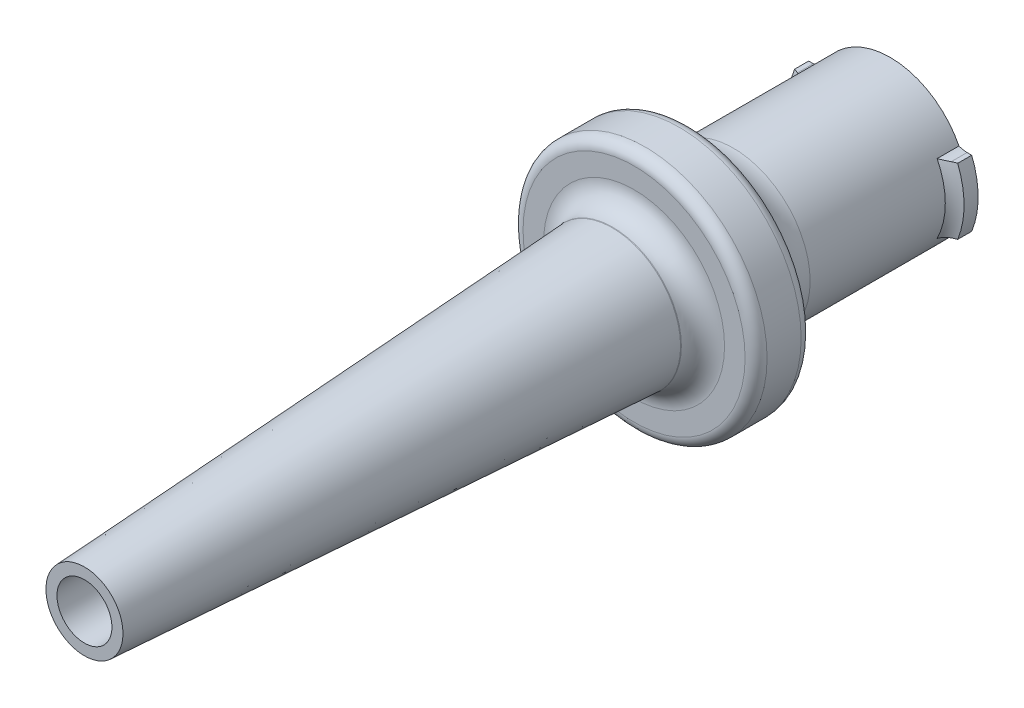
SolidWorks part; units mm, degrees
ref_plane "Front Plane" through (0, 0, 0) normal (0, 0, 1) x (1, 0, 0)
ref_plane "Top Plane" through (0, 0, 0) normal (0, 1, 0) x (1, 0, 0)
ref_plane "Right Plane" through (0, 0, 0) normal (1, 0, 0) x (0, 0, -1)
sketch "Sketch1" plane through (0, 0, 0) normal (0, 0, 1) x (1, 0, 0)
  line L1 (4, 1.5) -> (-4, 1.5)
  line L2 (4, 1.5) -> (4, -1.5)
  line L3 (4, -1.5) -> (-4, -1.5)
  line L4 (-4, 1.5) -> (-4, -1.5)
  circle A0 centre (0, 0) radius 4
  dimension "D1" = 4
  dimension "D2" = 4
  dimension "D3" = 1.5
  dimension "D4" = 3
extrude "Boss-Extrude1" add sketch "Sketch1" along normal blind 0.64 contours L1 A0 L3 region at (0, 0, 0)
sketch "Sketch2" plane through (0, 0, 0) normal (0, 0, -1) x (-1, 0, 0)
  circle A1 centre (0, 0) radius 3.3
extrude "Boss-Extrude2" add sketch "Sketch2" against normal blind 9.1
sketch "Sketch3" plane through (0, 0, 0) normal (0, 0, -1) x (-1, 0, 0)
  circle A0 centre (0, 0) radius 2.13
extrude "Cut-Extrude2" cut sketch "Sketch3" against normal blind 9.1 draft 4
sketch "Sketch4" plane through (0, 0, 9.1) normal (0, 0, 1) x (1, 0, 0)
  circle A0 centre (0, 0) radius 1.4937
  circle A1 centre (0, 0) radius 5.55
extrude "Boss-Extrude3" add sketch "Sketch4" along normal blind 2.55
sketch "Sketch8" plane through (0, 0, 11.65) normal (0, 0, 1) x (1, 0, 0)
  circle A0 centre (0, 0) radius 1.4937
  dimension "D1" = 2.9873
extrude "Boss-Extrude5" add sketch "Sketch8" along normal blind 25 separate body
sketch "Sketch9" plane through (0, 0, 11.65) normal (0, 0, 1) x (1, 0, 0)
  circle A0 centre (0, 0) radius 3.15
extrude "Boss-Extrude6" add sketch "Sketch9" along normal blind 25 draft 2
sketch "Sketch11" plane through (0, 0, 36.65) normal (0, 0, 1) x (1, 0, 0)
  circle A0 centre (0, 0) radius 1.495
extrude "Cut-Extrude7" cut sketch "Sketch11" against normal blind 25
fillet "Fillet6" radius 1 1 edges at (3.3, 0, 0.64)
fillet "Fillet7" radius 1 1 edges at (-3.3, 0, 0.64)
fillet "Fillet8" radius 1 4 edges at (-2.9394, -1.5, 0.797) (2.9394, -1.5, 0.797) (2.9394, 1.5, 0.797) (-2.9394, 1.5, 0.797)
fillet "Fillet10" radius 1 1 edges at (3.15, 0, 11.65)
fillet "Fillet11" radius 0.5 2 edges at (5.55, 0, 11.65) (5.55, 0, 9.1)
sketch "Sketch12" plane through (0, 0, 0) normal (0, 0, -1) x (-1, 0, 0)
  circle A0 centre (0, 0) radius 2.2
extrude "Cut-Extrude8" cut sketch "Sketch12" against normal blind 8 draft 5
sketch "Sketch14" plane through (0, 0, 0) normal (0, 0, -1) x (-1, 0, 0)
  circle A0 centre (0, 0) radius 2.25
extrude "Cut-Extrude9" cut sketch "Sketch14" against normal blind 9.1 draft 3
sketch "Sketch15" plane through (0, 0, 0) normal (0, 0, -1) x (-1, 0, 0)
  circle A0 centre (0, 0) radius 3.3
  circle A1 centre (0, 0) radius 3.5
extrude "Boss-Extrude7" add sketch "Sketch15" against normal blind 9
sketch "Sketch16" plane through (0, 0, 0) normal (0, 0, -1) x (-1, 0, 0)
  circle A0 centre (0, 0) radius 2.5
extrude "Cut-Extrude11" cut sketch "Sketch16" against normal blind 9 draft 2.5
sketch "Sketch19" plane through (0, 0, 36.65) normal (0, 0, 1) x (1, 0, 0)
  circle A0 centre (0, 0) radius 2
  circle A1 centre (0, 0) radius 3.1163
extrude "Cut-Extrude12" cut sketch "Sketch19" against normal blind 24
sketch "Sketch20" plane through (0, 0, 36.65) normal (0, 0, 1) x (1, 0, 0)
  circle A0 centre (0, 0) radius 1.25
  circle A1 centre (0, 0) radius 1.75
extrude "Boss-Extrude8" add sketch "Sketch20" against normal blind 24
sketch "Sketch22" plane through (0, 0, 36.65) normal (0, 0, 1) x (1, 0, 0)
  circle A0 centre (0, 0) radius 1.75
  circle A1 centre (0, 0) radius 2.6838
extrude "Cut-Extrude13" cut sketch "Sketch22" against normal blind 24
sketch "Sketch24" plane through (0, 0, 12.65) normal (0, 0, 1) x (1, 0, 0)
  circle A0 centre (0, 0) radius 3.1151
extrude "Boss-Extrude9" add sketch "Sketch24" along normal blind 24 draft 3.25
sketch "Sketch25" plane through (0, 0, 36.65) normal (0, 0, 1) x (1, 0, 0)
  circle A0 centre (0, 0) radius 1.25
extrude "Cut-Extrude14" cut sketch "Sketch25" against normal blind 24
sketch "Sketch26" plane through (0, 0, 0) normal (0, 0, -1) x (-1, 0, 0)
  circle A0 centre (0, 0) radius 3.5
  circle A1 centre (0, 0) radius 3.25
extrude "Boss-Extrude10" add sketch "Sketch26" against normal blind 9.5
fillet "Fillet12" radius 2 1 edges at (3.5, 0, 9.1)
sketch "Sketch28" plane through (0, 0, 9) normal (0, 0, -1) x (-1, 0, 0)
  circle A0 centre (0, 0) radius 2.1071
extrude "Cut-Extrude22" cut sketch "Sketch28" against normal blind 4
fillet "Fillet13" radius 2 1 edges at (-2.1071, 0, 13)
